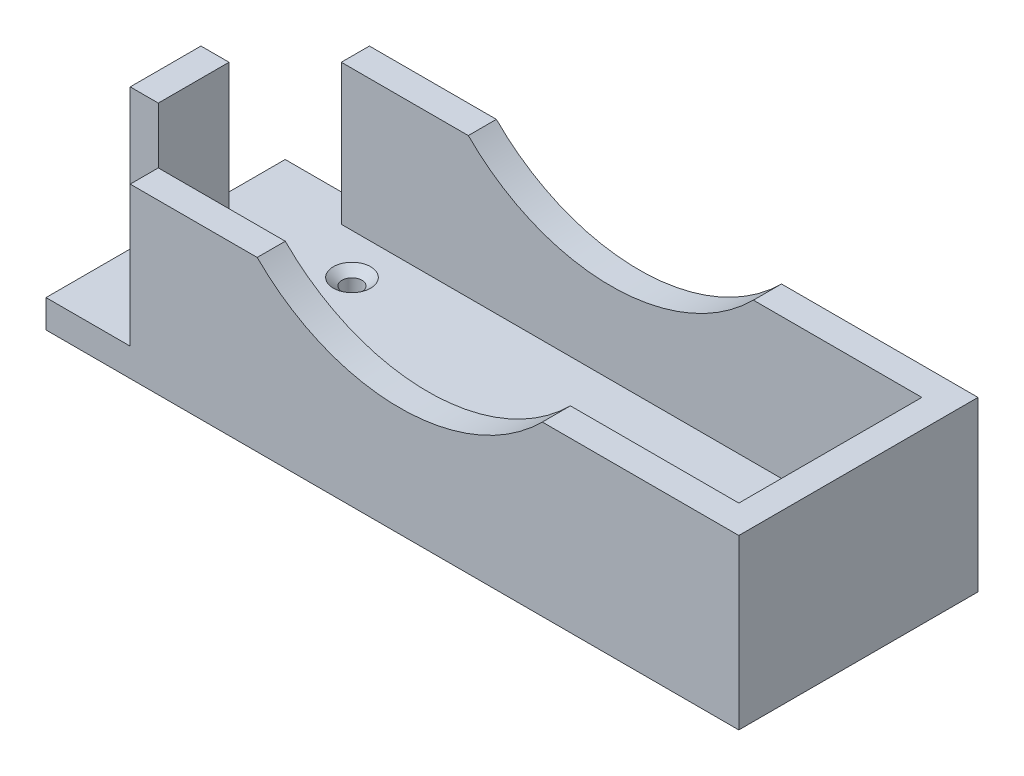
SolidWorks part; units mm, degrees
material "PET"
ref_plane "Front Plane" through (0, 0, 0) normal (0, 0, 1) x (1, 0, 0)
ref_plane "Top Plane" through (0, 0, 0) normal (0, 1, 0) x (1, 0, 0)
ref_plane "Right Plane" through (0, 0, 0) normal (1, 0, 0) x (0, 0, -1)
sketch "Sketch1" plane through (0, 0, 0) normal (0, 1, 0) x (1, 0, 0)
  line L5 (-69.4555, 10.1298) -> (74.5625, 10.1298)
  line L6 (-69.4555, 10.1298) -> (-69.4555, -31.2722)
  line L7 (-69.4555, -31.2722) -> (74.5625, -31.2722)
  line L8 (74.5625, 10.1298) -> (74.5625, -31.2722)
  line L9 (-75.8055, 16.4798) -> (80.9125, 16.4798)
  line L10 (-75.8055, 16.4798) -> (-75.8055, -37.6222)
  line L11 (-75.8055, -37.6222) -> (80.9125, -37.6222)
  line L12 (80.9125, 16.4798) -> (80.9125, -37.6222)
  line L14 (74.5625, 10.1298) -> (74.5625, 16.4798)
  line L15 (74.5625, -31.2722) -> (74.5625, -37.6222)
  line L16 (-56.7555, -31.2722) -> (-56.7555, -37.6222)
  line L17 (-75.8055, -18.5722) -> (-69.4555, -18.5722)
  line L18 (-69.4555, -31.2722) -> (-56.7555, -31.2722)
  line L19 (-75.8055, -31.2722) -> (-75.8055, -37.6222)
  line L20 (-75.8055, -37.6222) -> (-56.7555, -37.6222)
  line L21 (-56.7555, -31.2722) -> (-56.7555, -37.6222)
  line L22 (-75.8055, -18.5722) -> (-69.4555, -18.5722)
  line L23 (-75.8055, -18.5722) -> (-75.8055, -31.2722)
  line L25 (-69.4555, -18.5722) -> (-69.4555, -31.2722)
  line L26 (-75.8055, 16.4798) -> (-56.7555, 16.4798)
  line L27 (-75.8055, 16.4798) -> (-75.8055, 10.1298)
  line L28 (-69.4555, 10.1298) -> (-56.7555, 10.1298)
  line L29 (-56.7555, 16.4798) -> (-56.7555, 10.1298)
  line L30 (-75.8055, 16.4798) -> (-69.4555, 16.4798)
  line L31 (-75.8055, 16.4798) -> (-75.8055, -2.5702)
  line L32 (-75.8055, -2.5702) -> (-69.4555, -2.5702)
  line L33 (-69.4555, 10.1298) -> (-69.4555, -2.5702)
  point P0 (-49.1267, -9.4869)
  point P1 (-49.1267, 8.7015)
  point P2 (50.9319, 8.7015)
  point P3 (50.9319, -9.4869)
  point P8 (0, 0)
  dimension "D1" = 156.718
  dimension "D2" = 54.102
  dimension "D3" = 144.018
  dimension "D4" = 41.402
  dimension "D5" = 6.35
  dimension "D6" = 19.05
  dimension "D7" = 19.05
  dimension "D8" = 19.05
sketch "Sketch3" plane through (0, 0, 0) normal (0, 1, 0) x (1, 0, 0)
  line L1 (-69.4555, 10.1298) -> (74.5625, 10.1298)
  line L2 (-69.4555, 10.1298) -> (-69.4555, -31.2722)
  line L3 (-69.4555, -31.2722) -> (74.5625, -31.2722)
  line L4 (74.5625, 10.1298) -> (74.5625, -31.2722)
ref_plane "Plane2" through (72.39, 0, 0) normal (1, 0, 0) x (0, 0, -1)
extrude "Boss-Extrude1" add sketch "Sketch1" along normal blind 38.1 contours L8 L15 L11 L12 L9 L14 | L32 L10 L17 L6 region at (-72.6305, 0, 10.5712) region at (77.7375, 0, 10.5712)
extrude "Boss-Extrude2" add sketch "Sketch1<4>" along normal blind 6.35 contours L8 L5 L6 L7 | L6 L5 L8 L7 region at (2.5535, 0, 10.5712)
sketch "Sketch1<4>" plane through (0, 0, 0) normal (0, 1, 0) x (1, 0, 0) same geometry as "Sketch1"
extrude "Boss-Extrude3" add sketch "Sketch1<5>" along normal blind 38.1 contours L5 L14 L9 | L15 L7 L11 region at (8.9035, 0, -13.3048) region at (8.9035, 0, 34.4472)
sketch "Sketch1<5>" plane through (0, 0, 0) normal (0, 1, 0) x (1, 0, 0) same geometry as "Sketch1"
sketch "Sketch7" plane through (0, 6.35, 0) normal (0, 1, 0) x (1, 0, 0)
  line L4 (-69.4555, -2.5702) -> (-69.4555, -18.5722) construction
  line L5 (-56.7555, 16.4798) -> (80.9125, 16.4798) construction
  point P0 (-45.135, 0.9223)
  point P1 (-45.135, -21.9377)
  point P2 (50.115, -22.0012)
  point P3 (50.115, 0.8588)
  dimension "D1" = 22.86
  dimension "D2" = 22.86
  dimension "D3" = 95.25
  dimension "D4" = 95.25
  dimension "D5" = 24.3205
  dimension "D7" = 15.621
hole_wizard "CSK for #8 Flat Head Machine Screw (100)2" positions "Sketch8" profile "Sketch9" countersink size "#8" standard "ANSI Inch" end condition through all
sketch "Sketch8" plane through (0, 6.35, 0) normal (0, 1, 0) x (1, 0, 0)
  point P0 (-45.135, -21.9377)
  point P3 (-45.135, 0.9223)
  point P6 (50.115, 0.8588)
  point P9 (50.115, -22.0012)
sketch "Sketch9" plane through (-45.135, 6.35, 21.9377) normal (1, 0, 0) x (0, 0, 1)
  line L0 (0, 0) -> (0, 6.35)
  line L1 (0, 6.35) -> (2.2479, 6.35)
  line L2 (2.2479, 6.35) -> (2.2479, 1.6518)
  line L3 (2.2479, 1.6518) -> (4.2164, 0)
  line L5 (4.2164, 0) -> (0, 0)
  line L6 (-2.2479, 1.6518) -> (-4.2164, 0) construction
  line L11 (0, -6.35) -> (0, 107.95) construction
  dimension "Thru Hole Dia." = 4.4958
  dimension "Thru Hole Depth" = 6.35
  dimension "Near C'Sink Dia." = 8.4328
  dimension "Near C'Sink Angle" = 100
extrude "Boss-Extrude6" add sketch "Sketch1<8>" along normal blind 6.35 contours L17 L10 L11 L16 L7 L6 region at (-69.7249, 0, 24.9222)
sketch "Sketch1<8>" plane through (0, 0, 0) normal (0, 1, 0) x (1, 0, 0) same geometry as "Sketch1"
sketch "Sketch11" plane through (0, 0, 37.6222) normal (0, 0, 1) x (1, 0, 0)
  line L0 (-56.7555, 38.1) -> (80.9125, 38.1) construction
  line L1 (80.9125, 38.1) -> (80.9125, 0) construction
  line L2 (-28.03, 38.1) -> (36.4625, 38.1)
  arc A0 (36.4625, 38.1) -> (-28.03, 38.1) centre (4.2163, 70.3463) cw
  point P0 (-15.8864, 38.1)
  point P1 (12.0785, 38.1)
  dimension "D1" = 44.45
extrude "Cut-Extrude3" cut sketch "Sketch11" against normal through all and the other way through all
extrude "Boss-Extrude7" add sketch "Sketch1<9>" along normal blind 6.35 contours L10 L32 L6 L5 L29 L26 L9 region at (-69.7249, 0, -3.7798)
sketch "Sketch1<9>" plane through (0, 0, 0) normal (0, 1, 0) x (1, 0, 0) same geometry as "Sketch1"
